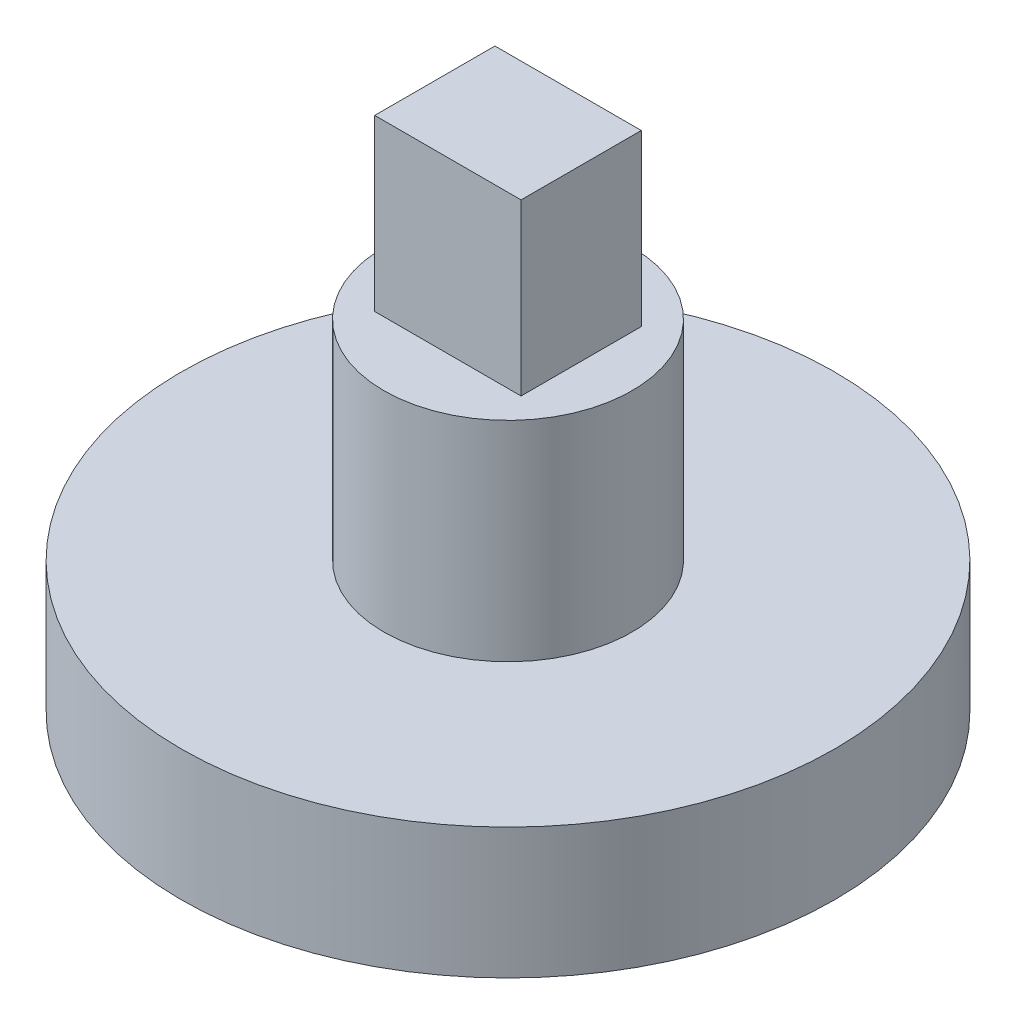
SolidWorks part; units mm, degrees
ref_plane "Front Plane" through (0, 0, 0) normal (0, 0, 1) x (1, 0, 0)
ref_plane "Top Plane" through (0, 0, 0) normal (0, 1, 0) x (1, 0, 0)
ref_plane "Right Plane" through (0, 0, 0) normal (1, 0, 0) x (0, 0, -1)
sketch "Sketch1" plane through (0, 0, 0) normal (0, 1, 0) x (1, 0, 0)
  line L0 (-2.8, -2.3) -> (-2.8, 2.3)
  line L1 (0, 8.3691) -> (0, -7.2355) construction
  line L2 (8.4023, 0) -> (-8.286, 0) construction
  line L3 (-2.8, 2.3) -> (2.8, 2.3)
  line L4 (2.8, -2.3) -> (2.8, 2.3)
  line L5 (-2.8, -2.3) -> (2.8, -2.3)
  circle A0 centre (0, 0) radius 12.5
  circle A1 centre (0, 0) radius 4.75
  point P13 (0, 2.3)
  point P14 (2.8, 0)
  point P15 (-2.8, 0)
  dimension "D1" = 25
  dimension "D2" = 9.5
  dimension "D3" = 5.6
  dimension "D4" = 4.6
extrude "Boss-Extrude1" add sketch "Sketch1" along normal blind 5 contours A0 A1 region at (-12.1464, 0, 0)
extrude "Boss-Extrude2" add sketch "Sketch1<3>" along normal blind 13 contours A1 L5 L0 L3 L4 region at (-4.6156, 0, 0)
sketch "Sketch1<3>" plane through (0, 0, 0) normal (0, 1, 0) x (1, 0, 0) same geometry as "Sketch1"
extrude "Boss-Extrude3" add sketch "Sketch1<4>" along normal blind 19.5 contours L0 L5 L4 L3 region at (0, 0, 0)
sketch "Sketch1<4>" plane through (0, 0, 0) normal (0, 1, 0) x (1, 0, 0) same geometry as "Sketch1"
sketch "Sketch2" plane through (0, 0, 0) normal (0, 1, 0) x (1, 0, 0)
  line L0 (-0.2882, -3.4881) -> (-12.2474, -2.5)
  line L1 (-0.2882, 3.4881) -> (-12.2474, 2.5)
  line L2 (0, 0) -> (-15.8071, 0) construction
  arc A0 (-0.2882, -3.4881) -> (-0.2882, 3.4881) centre (0, 0) ccw
  circle A1 centre (0, 0) radius 12.5 construction
  arc A2 (-12.2474, 2.5) -> (-12.2474, -2.5) centre (0, 0) ccw
  circle A3 centre (0, 0) radius 3.5
  dimension "D2" = 7
  dimension "D1" = 5
extrude "Cut-Extrude2" cut sketch "Sketch2" along normal blind 3 contours A3 L2 A2 L0 | L2 A3 L1 A2 | A0 A3 region at (-2.5019, 0, 2.3037) region at (-7.377, 0, 1.5193) region at (-7.377, 0, -1.5193)
extrude "Cut-Extrude3" cut sketch "Sketch2<3>" along normal blind 4 contours A0 A3 region at (0, 0, 0)
sketch "Sketch2<3>" plane through (0, 0, 0) normal (0, 1, 0) x (1, 0, 0) same geometry as "Sketch2"
